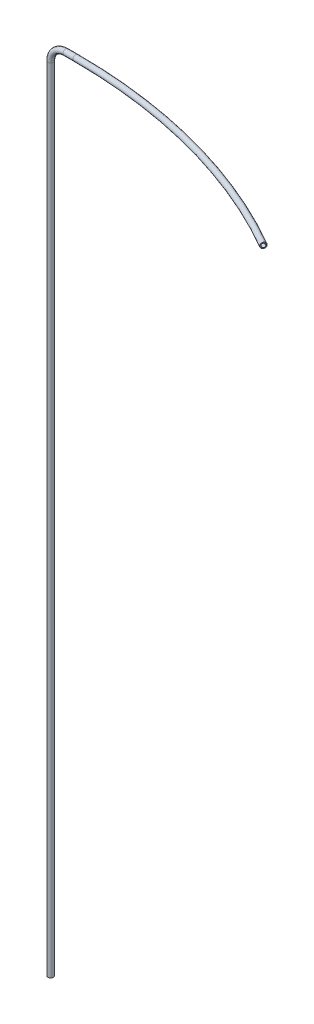
SolidWorks part; units mm, degrees
note: '?' marks a value the reader was unsure of.
ref_plane "前视基准面" through (0, 0, 0) normal (0, 0, 1) x (1, 0, 0)
ref_plane "上视基准面" through (0, 0, 0) normal (0, 1, 0) x (1, 0, 0)
ref_plane "右视基准面" through (0, 0, 0) normal (1, 0, 0) x (0, 0, -1)
sketch "草图10" plane through (0, 0, 0) normal (0, 1, 0) x (1, 0, 0)
  line L0 (0, 0) -> (0, 200)
ref_axis "基准轴3" through (0, 0, -200) along (0, 1, 0)
sketch "草图1" plane through (0, 0, 0) normal (1, 0, 0) x (0, 0, -1)
  line L0 (1300, -0.3711) -> (0, 0)
  line L1 (0, 139.1195) -> (0, -57.917) construction
  circle A0 centre (1300, -0.3711) radius 6
  circle A1 centre (1300, -0.3711) radius 4
  dimension "D1" = 12
  dimension "D2" = 8
  dimension "D3" = 1300
revolve "旋转1" add sketch "草图1" angle 30 about axis through (0, 0, -200) along (0, 1, 0)
sketch "草图2" plane through (0, 0, 0) normal (-1, 0, 0) x (0, 0, 1)
  line L0 (-500, -31.0864) -> (-500, 27.4301) construction
  circle A0 centre (-500, -0.3711) radius 10
  circle A1 centre (-500, -0.3711) radius 15
  circle A4 centre (-1300, -0.3711) radius 4
  circle A5 centre (-1300, -0.3711) radius 6
ref_plane "基准面1" through (0, 0, -500) normal (0, 0, -1) x (0, 1, 0)
sketch "草图3" plane through (0, 0, -500) normal (0, 0, -1) x (0, 1, 0)
  line L0 (0, 0) -> (0, -21.3411)
  line L1 (-32.7423, -54.0834) -> (-932.7423, -54.0834)
  arc A0 (0, -21.3411) -> (-32.7423, -54.0834) centre (-32.7423, -21.3411) cw
  dimension "D1" = 900
sweep "扫描1" add profiles "草图2" path "草图3"
sketch "草图5" plane through (0, 0, 0) normal (1, 0, 0) x (0, 0, -1)
  line L0 (0, 0) -> (1300, 0)
  line L1 (1300, 0) -> (1300, 54.7405)
ref_axis "基准轴1" through (0, 0, -1300) along (0, 1, 0)?
ref_plane "基准面2" through (0, 0, -1300) normal (0, 0, -1) x (-1, 0, 0)
sketch "草图6" plane through (0, 0, 0) normal (0, 1, 0) x (1, 0, 0)
  line L0 (553, 1157.8241) -> (547, 1147.4318)
  line L2 (-21.3411, 1306) -> (-21.3411, 1294) construction
  point P0 (-53.7124, 1300)
  point P9 (-21.3411, 1300)
  point P13 (0, 1300)
sketch "草图11" plane through (0, -932.7423, 0) normal (0, -1, 0) x (1, 0, 0)
  circle A0 centre (-53.7124, -1300) radius 4 construction
  circle A1 centre (-53.7124, -1300) radius 6
  circle A2 centre (-53.7124, -1300) radius 6
  circle A3 centre (-53.7124, -1300) radius 4
  dimension "D1" = 0
extrude "凸台-拉伸1" add sketch "草图11" along normal blind 800
